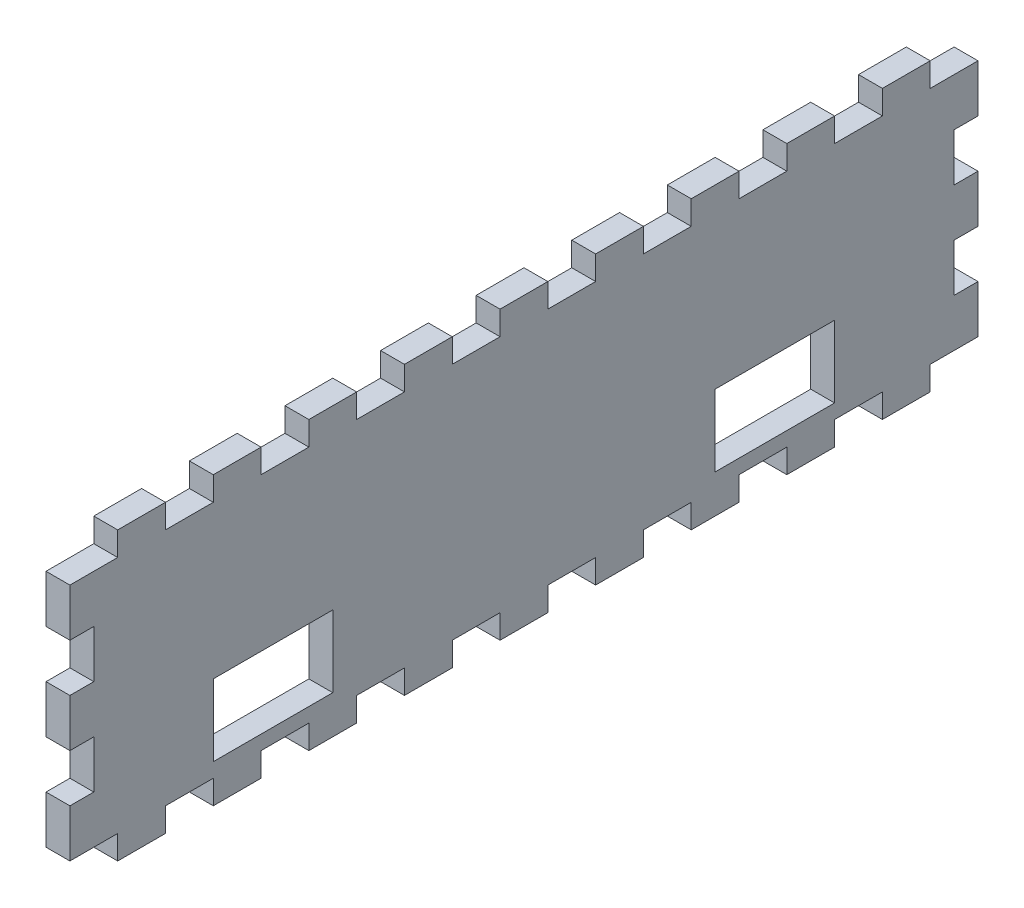
SolidWorks part; units mm, degrees
ref_plane "Front Plane" through (0, 0, 0) normal (0, 0, 1) x (1, 0, 0)
ref_plane "Top Plane" through (0, 0, 0) normal (0, 1, 0) x (1, 0, 0)
ref_plane "Right Plane" through (0, 0, 0) normal (1, 0, 0) x (0, 0, -1)
sketch "Sketch2" plane through (0, 0, 0) normal (1, 0, 0) x (0, 0, -1)
  line L6 (-30.0896, -3.3632) -> (-30.0896, 1.6368)
  line L7 (-30.0896, 1.6368) -> (-40.0896, 1.6368)
  line L8 (-40.0896, 1.6368) -> (-40.0896, -3.3632)
  line L9 (-40.0896, -3.3632) -> (-50.0896, -3.3632)
  line L10 (-50.0896, -3.3632) -> (-50.0896, 1.6368)
  line L11 (-50.0896, 1.6368) -> (-60.0896, 1.6368)
  line L12 (-60.0896, 1.6368) -> (-60.0896, -3.3632)
  line L13 (-60.0896, -3.3632) -> (-70.0896, -3.3632)
  line L14 (-70.0896, -3.3632) -> (-70.0896, 1.6368)
  line L15 (-70.0896, 1.6368) -> (-80.0896, 1.6368)
  line L16 (-80.0896, 1.6368) -> (-80.0896, -3.3632)
  line L17 (-80.0896, -3.3632) -> (-90.0896, -3.3632)
  line L18 (-90.0896, -3.3632) -> (-90.0896, 1.6368)
  line L19 (-90.0896, 1.6368) -> (-100.0896, 1.6368)
  line L20 (-100.0896, 1.6368) -> (-100.0896, -3.3632)
  line L21 (-100.0896, -3.3632) -> (-110.0896, -3.3632)
  line L22 (-110.0896, -3.3632) -> (-110.0896, 1.6368)
  line L23 (-110.0896, 1.6368) -> (-120.0896, 1.6368)
  line L24 (-120.0896, 1.6368) -> (-120.0896, -3.3632)
  line L25 (-120.0896, -3.3632) -> (-130.0896, -3.3632)
  line L26 (-130.0896, -3.3632) -> (-130.0896, 1.6368)
  line L27 (-130.0896, 1.6368) -> (-140.0896, 1.6368)
  line L28 (-140.0896, 1.6368) -> (-140.0896, -3.3632)
  line L29 (-140.0896, -3.3632) -> (-150.0896, -3.3632)
  line L30 (-150.0896, -3.3632) -> (-150.0896, 1.6368)
  line L31 (-150.0896, 1.6368) -> (-160.0896, 1.6368)
  line L32 (-160.0896, 1.6368) -> (-160.0896, -3.3632)
  line L33 (-160.0896, -3.3632) -> (-170.0896, -3.3632)
  line L34 (-170.0896, -3.3632) -> (-170.0896, 1.6368)
  line L35 (-170.0896, 1.6368) -> (-180.0896, 1.6368)
  line L36 (-180.0896, 1.6368) -> (-180.0896, -3.3632)
  line L37 (-180.0896, -3.3632) -> (-190.0896, -3.3632)
  line L38 (-190.0896, -3.3632) -> (-190.0896, 1.6368)
  line L39 (-190.0896, 1.6368) -> (-200.0896, 1.6368)
  line L40 (-200.0896, 1.6368) -> (-200.0896, -3.3632)
  line L63 (-200.0896, 17.5016) -> (-30.0896, 17.5016) construction
  line L64 (-115.0896, 17.5016) -> (-115.0896, 22.1756) construction
  line L89 (-200.0896, -3.3632) -> (-210.0896, -3.3632)
  line L137 (-210.0896, -3.3632) -> (-210.0896, -13.3632)
  line L198 (-210.0896, -13.3632) -> (-205.0896, -13.3632)
  line L199 (-205.0896, -13.3632) -> (-205.0896, -23.3632)
  line L264 (-205.0896, -23.3632) -> (-210.0896, -23.3632)
  line L269 (-210.0896, -23.3632) -> (-210.0896, -33.3632)
  line L270 (-210.0896, -33.3632) -> (-205.0896, -33.3632)
  line L271 (-205.0896, -33.3632) -> (-205.0896, -43.3632)
  line L272 (-205.0896, -43.3632) -> (-210.0896, -43.3632)
  line L273 (-210.0896, -43.3632) -> (-210.0896, -53.3632)
  line L274 (-210.0896, -53.3632) -> (-200.0896, -53.3632)
  line L275 (-227.2315, -3.3632) -> (-227.2315, -53.3632) construction
  line L276 (-227.2315, -28.3632) -> (-233.7306, -28.3632) construction
  line L277 (-200.0896, -58.3632) -> (-200.0896, -53.3632)
  line L278 (-190.0896, -58.3632) -> (-200.0896, -58.3632)
  line L279 (-190.0896, -53.3632) -> (-190.0896, -58.3632)
  line L280 (-180.0896, -53.3632) -> (-190.0896, -53.3632)
  line L281 (-180.0896, -58.3632) -> (-180.0896, -53.3632)
  line L282 (-170.0896, -58.3632) -> (-180.0896, -58.3632)
  line L283 (-170.0896, -53.3632) -> (-170.0896, -58.3632)
  line L284 (-160.0896, -53.3632) -> (-170.0896, -53.3632)
  line L285 (-160.0896, -58.3632) -> (-160.0896, -53.3632)
  line L286 (-150.0896, -58.3632) -> (-160.0896, -58.3632)
  line L287 (-150.0896, -53.3632) -> (-150.0896, -58.3632)
  line L288 (-140.0896, -53.3632) -> (-150.0896, -53.3632)
  line L289 (-140.0896, -58.3632) -> (-140.0896, -53.3632)
  line L290 (-130.0896, -58.3632) -> (-140.0896, -58.3632)
  line L291 (-130.0896, -53.3632) -> (-130.0896, -58.3632)
  line L292 (-120.0896, -53.3632) -> (-130.0896, -53.3632)
  line L293 (-120.0896, -58.3632) -> (-120.0896, -53.3632)
  line L294 (-110.0896, -58.3632) -> (-120.0896, -58.3632)
  line L295 (-110.0896, -53.3632) -> (-110.0896, -58.3632)
  line L296 (-100.0896, -53.3632) -> (-110.0896, -53.3632)
  line L297 (-100.0896, -58.3632) -> (-100.0896, -53.3632)
  line L298 (-90.0896, -58.3632) -> (-100.0896, -58.3632)
  line L299 (-90.0896, -53.3632) -> (-90.0896, -58.3632)
  line L300 (-80.0896, -53.3632) -> (-90.0896, -53.3632)
  line L301 (-80.0896, -58.3632) -> (-80.0896, -53.3632)
  line L302 (-70.0896, -58.3632) -> (-80.0896, -58.3632)
  line L303 (-70.0896, -53.3632) -> (-70.0896, -58.3632)
  line L304 (-60.0896, -53.3632) -> (-70.0896, -53.3632)
  line L305 (-60.0896, -58.3632) -> (-60.0896, -53.3632)
  line L306 (-50.0896, -58.3632) -> (-60.0896, -58.3632)
  line L307 (-50.0896, -53.3632) -> (-50.0896, -58.3632)
  line L308 (-40.0896, -53.3632) -> (-50.0896, -53.3632)
  line L309 (-40.0896, -58.3632) -> (-40.0896, -53.3632)
  line L310 (-30.0896, -58.3632) -> (-40.0896, -58.3632)
  line L311 (-30.0896, -53.3632) -> (-30.0896, -58.3632)
  line L312 (-20.0896, -53.3632) -> (-30.0896, -53.3632)
  line L313 (-20.0896, -43.3632) -> (-20.0896, -53.3632)
  line L314 (-25.0896, -43.3632) -> (-20.0896, -43.3632)
  line L315 (-25.0896, -33.3632) -> (-25.0896, -43.3632)
  line L316 (-20.0896, -33.3632) -> (-25.0896, -33.3632)
  line L317 (-20.0896, -23.3632) -> (-20.0896, -33.3632)
  line L318 (-25.0896, -23.3632) -> (-20.0896, -23.3632)
  line L319 (-25.0896, -13.3632) -> (-25.0896, -23.3632)
  line L320 (-20.0896, -13.3632) -> (-25.0896, -13.3632)
  line L321 (-20.0896, -3.3632) -> (-20.0896, -13.3632)
  line L322 (-30.0896, -3.3632) -> (-20.0896, -3.3632)
  point P100 (-20.0896, -28.3632)
  dimension "D1" = 10
  dimension "D2" = 10
  dimension "D3" = 5
  dimension "D4" = 10
  dimension "D5" = 10
  dimension "D6" = 10
  dimension "D8" = 5
  dimension "D9" = 190
  dimension "D10" = 60
  dimension "D7" = 10
extrude "Boss-Extrude3" add sketch "Sketch2" along normal blind 5 contours L38 L39 L40 L89 L137 L198 L199 L264 L269 L270 L271 L272 L273 L274 L277 L278 L279 L280 L281 L282 L283 L284 L285 L286 L287 L288 L289 L290 L291 L292 L293 L294 L295 L296 L297 L298 L299 L300 L301 L302 L303 L304 L305 L306 L307 L308 L309 L310 L311 L312 L313 L314 L315 L316 L317 L318 L319 L320 L321 L322 L6 L7 L8 L9 L10 L11 L12 L13 L14 L15 L16 L17 L18 L19 L20 L21 L22 L23 L24 L25 L26 L27 L28 L29 L30 L31 L32 L33 L34 L35 L36 L37
sketch "Sketch3" plane through (5, 0, 0) normal (1, 0, 0) x (0, 0, -1)
  line L0 (-210.0896, -53.3632) -> (-210.0896, -71.579) construction
  line L5 (-210.0896, -71.579) -> (-20.0896, -71.579) construction
  line L6 (-20.0896, -71.579) -> (-20.0896, -53.3632) construction
  line L7 (-115.0896, -71.579) -> (-115.0896, -65.5307) construction
  line L12 (-150.0896, -53.3632) -> (-150.0896, -58.3632) construction
  line L13 (-180.0896, -50.3632) -> (-155.0896, -50.3632)
  line L14 (-180.0896, -50.3632) -> (-180.0896, -35.3632)
  line L15 (-180.0896, -35.3632) -> (-155.0896, -35.3632)
  line L16 (-155.0896, -50.3632) -> (-155.0896, -35.3632)
  line L17 (-50.0896, -35.3632) -> (-75.0896, -35.3632)
  line L18 (-75.0896, -50.3632) -> (-75.0896, -35.3632)
  line L19 (-50.0896, -50.3632) -> (-75.0896, -50.3632)
  line L20 (-50.0896, -50.3632) -> (-50.0896, -35.3632)
  dimension "D1" = 3
  dimension "D2" = 5
  dimension "D3" = 190
  dimension "D4" = 25
  dimension "D5" = 15
extrude "Cut-Extrude1" cut sketch "Sketch3" against normal blind 10
